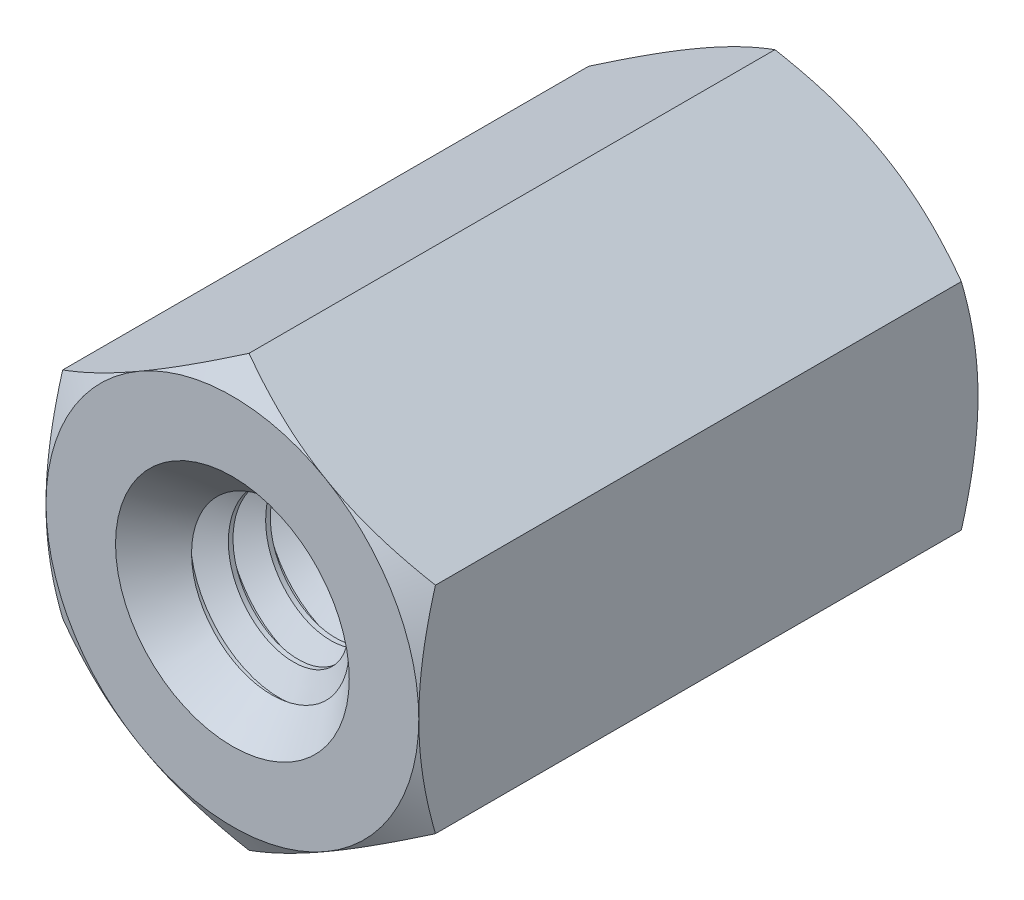
SolidWorks part; units mm, degrees
ref_plane "Front Plane" through (0, 0, 0) normal (0, 0, 1) x (1, 0, 0)
ref_plane "Top Plane" through (0, 0, 0) normal (0, 1, 0) x (1, 0, 0)
ref_plane "Right Plane" through (0, 0, 0) normal (1, 0, 0) x (0, 0, -1)
sketch "Sketch1" plane through (0, 0, 0) normal (0, 0, 1) x (1, 0, 0)
  line L1 (0, 2.3094) -> (-2, 1.1547)
  line L2 (-2, 1.1547) -> (-2, -1.1547)
  line L3 (-2, -1.1547) -> (0, -2.3094)
  line L4 (0, -2.3094) -> (2, -1.1547)
  line L5 (2, -1.1547) -> (2, 1.1547)
  line L6 (2, 1.1547) -> (0, 2.3094)
  circle A0 centre (0, 0) radius 2 construction
  dimension "Hex" = 4
extrude "Extrude1" add sketch "Sketch1" against normal blind 6
sketch "Sketch2" plane through (0, 0, 0) normal (0, 0, 1) x (1, 0, 0)
  circle A0 centre (0, 0) radius 2 construction
  circle A1 centre (0, 0) radius 2
extrude "Cut-Extrude1" cut sketch "Sketch2" against normal through all draft 60 flip side to cut
sketch "Sketch3" plane through (0, 0, -6) normal (0, 0, -1) x (-1, 0, 0)
  circle A1 centre (0, 0) radius 2
  circle A2 centre (0, 0) radius 2
  dimension "D1" = 0
extrude "Cut-Extrude2" cut sketch "Sketch3" against normal through all draft 60 flip side to cut
sketch "Sketch4" plane through (0, 0, 0) normal (0, 0, 1) x (1, 0, 0)
  circle A0 centre (0, 0) radius 1
  dimension "Thread Dia" = 2
extrude "Cut-Extrude3" cut sketch "Sketch4" against normal through all
sketch "Sketch7" plane through (0, 0, 0) normal (0, 0, 1) x (1, 0, 0)
  circle A4 centre (0, 0) radius 1.254
  circle A5 centre (0, 0) radius 1.254
  dimension "D1" = 0.254
sketch "Sketch8" plane through (0, 0, -6) normal (0, 0, -1) x (-1, 0, 0)
  circle A1 centre (0, 0) radius 1.254
  circle A2 centre (0, 0) radius 1.254 construction
sketch "Sketch5" plane through (0, 0, 0) normal (0, 0, 1) x (1, 0, 0)
  circle A0 centre (0, 0) radius 1 construction
  circle A1 centre (0, 0) radius 1
curve "Helix/Spiral1" pitch 0.4 height 6.4 radius 1 centre (0, 0, 0) axis (0, 0, -1) start towards (0, 1, 0) parameters "pitch"=0.4
sketch "Sketch9" plane through (0, 0, 0) normal (1, 0, 0) x (0, 0, -1)
  line L0 (-0.2, 1) -> (-0.15, 1)
  line L1 (-0.15, 1) -> (0, 0.7402)
  line L2 (-0.2, 1) -> (-0.35, 0.7402)
  line L3 (-0.35, 0.7402) -> (0, 0.7402)
  line L4 (-0.175, 1) -> (-0.175, 0.7402) construction
  line L5 (-0.275, 0.8701) -> (-0.075, 0.8701) construction
  line L7 (0, 0.7402) -> (0, 1) construction
  line L8 (0, 1) -> (0, -1) construction
  dimension "D1" = 0.05
  dimension "D2" = 0.2
  dimension "D3" = 60
sketch "Sketch12" plane through (0, 0, 0) normal (0, 0, 1) x (1, 0, 0)
  circle A0 centre (0, 0) radius 0.7402
  circle A1 centre (0, 0) radius 1 construction
  circle A2 centre (0, 0) radius 1
extrude "Extrude2" add sketch "Sketch12" against normal up to surface (6 mm away) up to face at (1, 0, -6)
sweep "Cut-Sweep1" cut profiles "Sketch9" path "Helix/Spiral1" align with end faces yes
extrude "Cut-Extrude6" cut sketch "Sketch7" against normal through all draft 45
extrude "Cut-Extrude7" cut sketch "Sketch8" against normal through all draft 45
equation "\"D2@Sketch9\" = \"pitch@Helix/Spiral1\"*.5"
equation "\"D3@Helix/Spiral1\" = \"pitch@Helix/Spiral1\"+\"Height@Extrude1\""
equation "\"D1@Sketch9\" = \"pitch@Helix/Spiral1\"*.125"
